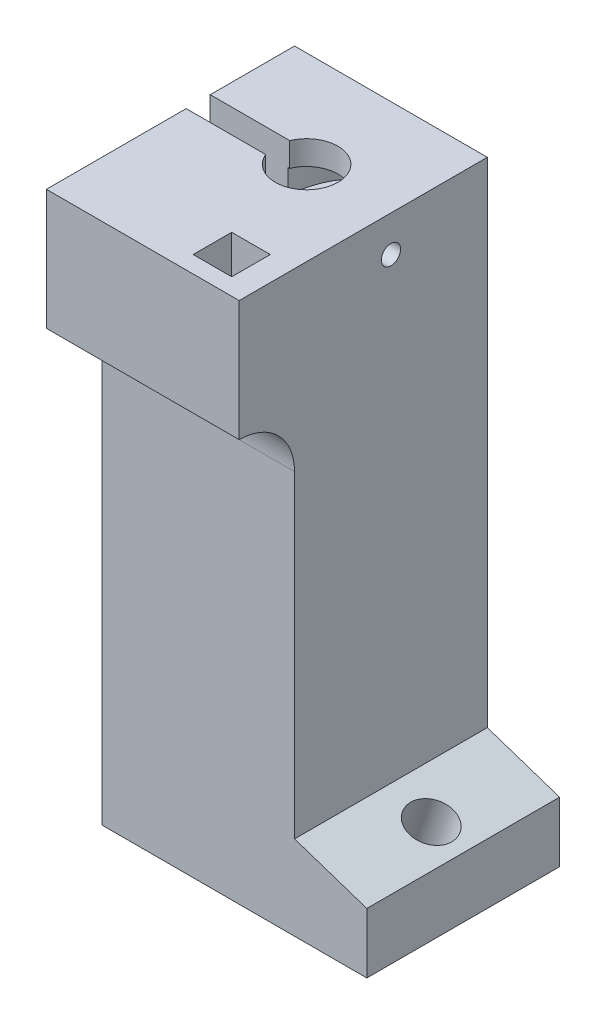
SolidWorks part; units mm, degrees
ref_plane "Front Plane" through (0, 0, 0) normal (0, 0, 1) x (1, 0, 0)
ref_plane "Top Plane" through (0, 0, 0) normal (0, 1, 0) x (1, 0, 0)
ref_plane "Right Plane" through (0, 0, 0) normal (1, 0, 0) x (0, 0, -1)
sketch "VerticalAxis" plane through (0, 0, 0) normal (0, 0, 1) x (1, 0, 0)
  line L0 (0, 0) -> (0, 42.951) construction
sketch "MainRotationalDesign" plane through (13.9419, 0, 0) normal (0, 0, -1) x (0, -1, 0)
  line L2 (5, 13.9419) -> (26.7642, 13.9419) construction
  line L3 (0, 13.9419) -> (-19.7322, 13.9419)
  line L4 (-7.75, 13.9419) -> (-7.75, 7.1919)
  point P0 (0, 13.9419)
  point P4 (0, 0)
  point P5 (0, 0)
  point P10 (0, 0)
  point P11 (0, 0)
  point P14 (5.666, 13.9419)
  dimension "D4" = 7.75
  dimension "D3" = 6.75
ref_plane "SingleChannelBasePlane" through (0, 7.75, 0) normal (0, 1, 0) x (0.9967, 0, 0.0811)
sketch "ShuttleOutline" plane through (-33.8949, 7.75, -2.7565) normal (0, 1, 0) x (0.9967, 0, 0.0811)
  line L0 (33.946, 0.7475) -> (38.9052, 1.4518) construction
  line L3 (39.0755, -0.6413) -> (34.0676, -0.7475) construction
  line L4 (36.4256, 1.0997) -> (36.9215, 1.1701)
  line L7 (36.9215, 1.1701) -> (36.9515, 0.8013)
  line L8 (36.4256, 1.0997) -> (33.9338, 0.897)
  line L9 (36.4256, 1.0997) -> (36.5715, -0.6944) construction
  line L10 (36.5715, -0.6944) -> (34.0797, -0.897)
  line L11 (33.9338, 0.897) -> (34.0797, -0.897) construction
  line L12 (36.9191, 1.2) -> (37.4175, 1.2405) construction
  line L13 (36.9191, 1.2) -> (36.9515, 0.8013) construction
  line L14 (36.9515, 0.8013) -> (37.4499, 0.8419)
  line L15 (37.4175, 1.2405) -> (37.4499, 0.8419)
  line L16 (37.5407, -0.2745) -> (37.0423, -0.315)
  line L17 (37.5407, -0.2745) -> (37.5731, -0.6731)
  line L18 (37.5731, -0.6731) -> (37.0747, -0.7137) construction
  line L19 (37.0423, -0.315) -> (37.0747, -0.7137) construction
  line L21 (36.5715, -0.6944) -> (37.0723, -0.6838)
  line L22 (37.0723, -0.6838) -> (37.0423, -0.315)
  line L23 (37.4175, 1.2405) -> (38.9052, 1.4518)
  line L24 (39.0755, -0.6413) -> (37.5731, -0.6731)
  line L25 (37.3414, 0.2712) -> (32.4051, -0.1303) construction
  line L26 (38.9052, 1.4518) -> (39.0755, -0.6413) construction
  line L27 (33.946, 0.7475) -> (34.0676, -0.7475) construction
  line L31 (34.0068, 0) -> (40.7346, 0.5471) construction
  circle A2 centre (38.9903, 0.4053) radius 0.6 construction
  circle A3 centre (38.9903, 0.4053) radius 0.4 construction
  circle A4 centre (34.0068, 0) radius 0.35 construction
  circle A5 centre (38.9903, 0.4053) radius 1.05 construction
  circle A6 centre (34.0068, 0) radius 0.75 construction
  arc A7 (33.9338, 0.897) -> (34.0797, -0.897) centre (34.0068, 0) ccw
  arc A8 (38.9052, 1.4518) -> (39.0755, -0.6413) centre (38.9903, 0.4053) cw
  point P4 (37.0723, -0.6838)
  point P15 (34.0068, 0)
  point P16 (36.9215, 1.1701)
  dimension "D2" = 1.2
  dimension "D3" = 0.8
  dimension "D4" = 0.7
  dimension "D1" = 1.5
  dimension "D5" = 2.1
  dimension "D6" = 5
  dimension "D10" = 1.8
  dimension "D9" = 2.5
  dimension "D11" = 2.5
  dimension "D12" = 0.5
  dimension "D14" = 1.5
  dimension "D7" = 0.4
sketch "ShuttleChannelOutline" plane through (33.8949, 7.75, 2.7565) normal (0, -1, 0) x (-0.9967, 0, -0.0811)
  line L0 (29.1854, 2.3987) -> (28.8611, -1.5881) construction
  line L1 (27.1169, -1.4463) -> (31.1037, -1.7705)
  line L2 (27.1169, -1.4463) -> (27.4411, 2.5405)
  line L3 (27.4411, 2.5405) -> (31.428, 2.2163)
  line L4 (31.1037, -1.7705) -> (31.428, 2.2163)
  line L5 (34.0068, 0) -> (27.279, 0.5471) construction
  line L6 (29.1084, 1.4518) -> (28.9381, -0.6413) construction
  line L8 (-199311.2371, 16211.4774) -> (199377.5178, -16211.3364) construction
  point P13 (27.279, 0.5471)
  point P16 (31.2658, 0.2229)
  dimension "D2" = 4
  dimension "D1" = 4
extrude "ShuttleChannelBody-Extrude" add sketch "ShuttleChannelOutline" against normal blind 10
sketch "Sketch23" plane through (0, 17.75, 0) normal (0, 1, 0) x (0.9959, 0, -0.09)
  line L0 (6.5427, -2.5991) -> (6.9025, 1.3847)
  line L1 (6.9025, 1.3847) -> (2.9188, 1.7445)
  line L2 (2.9188, 1.7445) -> (2.5589, -2.2393)
  line L3 (2.5589, -2.2393) -> (6.5427, -2.5991)
  line L4 (2.5589, -2.2393) -> (2.9188, 1.7445) construction
  circle A0 centre (4.9797, -0.4498) radius 0.425
  point P6 (0, 0)
  dimension "D1" = 0.85
extrude "ShuttleChannelCap-Extrude1" add sketch "Sketch23" along normal blind 1
sketch "Sketch22" plane through (0, 18.75, 0) normal (0, 1, 0) x (0.9909, 0, -0.1349)
  line L0 (6.4185, -2.8923) -> (2.4551, -2.3527)
  line L1 (2.4551, -2.3527) -> (2.9947, 1.6107)
  line L2 (2.9947, 1.6107) -> (6.9581, 1.0711)
  line L3 (6.9581, 1.0711) -> (6.4185, -2.8923)
  line L4 (5.0959, 0.3659) -> (4.8127, -1.7149) construction
  line L5 (0, 0) -> (6.6883, -0.9106) construction
  circle A0 centre (4.9543, -0.6745) radius 0.65 construction
  ellipse E0 centre (4.9543, -0.6745) end of major axis (5.1297, 0.6136) minor radius 0.65
  dimension "D1" = 1.3
  dimension "D2" = 2.6
extrude "ShuttleChannelCap-Extrude2" add sketch "Sketch22" along normal blind 0.5
sketch "Sketch24" plane through (0, 19.25, 0) normal (0, 1, 0) x (0.9909, 0, -0.1349)
  line L0 (6.4185, -2.8923) -> (6.9581, 1.0711)
  line L1 (6.9581, 1.0711) -> (2.9947, 1.6107)
  line L2 (2.9947, 1.6107) -> (2.4551, -2.3527)
  line L3 (2.4551, -2.3527) -> (6.4185, -2.8923)
  circle A0 centre (4.9543, -0.6745) radius 0.65
  circle A1 centre (4.9543, -0.6745) radius 0.65 construction
extrude "ShuttleChannelCap-Extrude3" add sketch "Sketch24" along normal blind 0.5
sketch "Sketch25" plane through (0, 19.75, 0) normal (0, 1, 0) x (0.9909, 0, -0.1349)
  line L2 (2.9947, 1.6107) -> (2.4551, -2.3527) construction
  line L4 (2.7586, -0.1233) -> (4.3935, -0.3458)
  line L5 (4.3935, -0.3458) -> (4.3261, -0.8413)
  line L6 (4.3261, -0.8413) -> (2.6911, -0.6187)
  line L7 (2.6911, -0.6187) -> (2.7586, -0.1233)
  circle A0 centre (4.9543, -0.6745) radius 0.65 construction
  point P2 (2.7249, -0.371)
  dimension "D1" = 0.5
extrude "ShuttleChannelCap-InjectionChannel" cut sketch "Sketch25" against normal up to surface (1 mm away) up to face at (4.575, 18.75, 0)
sketch "Sketch26" plane through (6.75, 0, 0) normal (-1, 0, 0) x (0, -0.8752, -0.4838)
  line L0 (-6.7828, -3.7491) -> (-16.6288, -9.1914) construction
  line L1 (-7.7503, -1.9987) -> (-5.8153, -5.4995) construction
  line L3 (-18.2528, -7.8038) -> (-16.3177, -11.3046) construction
  circle A0 centre (-16.6288, -9.1914) radius 0.2
  dimension "D1" = 0.4
  dimension "D2" = 0.75
extrude "ShuttleChannelCap-InjectionHole" cut sketch "Sketch26" along normal through all
fillet "ShuttleChannelCap-InjectionHole-Fillet" radius 0.25 1 edges at (5.6427, 18.9547, 0.1948)
extrude "Channel-Cut-Extrude12" cut sketch "ShuttleOutline" along normal blind 10 and the other way blind 5
fillet "Fillet1" radius 0.125 4 edges at (3, 12.75, 0.56) (3.5, 12.75, 0.56) (3.5, 12.75, -0.56) (3, 12.75, -0.56)
sketch "Sketch27" plane through (0, 0, 2) normal (0, 0, 1) x (1, 0, 0)
  line L0 (6.75, 7.75) -> (8.25, 7.75)
  line L1 (8.25, 7.75) -> (8.25, 9)
  line L2 (8.25, 9) -> (6.75, 9.5)
  line L3 (6.75, 19.75) -> (6.75, 7.75) construction
  line L4 (6.75, 9.5) -> (6.75, 7.75)
  dimension "D1" = 1.5
  dimension "D2" = 1.25
  dimension "D3" = 1.75
extrude "Boss-Extrude1" add sketch "Sketch27" against normal up to surface (4 mm away) up to face at (4.75, 13.75, -2)
sketch "Sketch28" plane through (3.525, 10.575, 0) normal (0.3162, 0.9487, 0) x (0.9487, -0.3162, 0)
  line L0 (4.9806, 0) -> (4.2806, 0) construction
  line L1 (4.9806, 2) -> (4.9806, -2) construction
  circle A0 centre (4.2806, 0) radius 0.45
  dimension "D1" = 0.9
  dimension "D2" = 0.7
extrude "Cut-Extrude1" cut sketch "Sketch28" against normal through all contours A0
sketch "Sketch29" plane through (0, 0, 2) normal (0, 0, 1) x (1, 0, 0)
  line L0 (2.75, 19.75) -> (2.75, 7.75) construction
  line L1 (6.75, 19.75) -> (2.75, 19.75)
  line L2 (6.75, 19.75) -> (6.75, 17.25)
  line L3 (6.75, 17.25) -> (2.75, 17.25)
  line L4 (2.75, 19.75) -> (2.75, 17.25)
  dimension "D1" = 2.5
extrude "Boss-Extrude2" add sketch "Sketch29" along normal blind 1.15
fillet "Fillet2" radius 1.15 1 edges at (4.75, 17.25, 2)
sketch "Sketch30" plane through (0, 19.75, 0) normal (0, 1, 0) x (1, 0, 0)
  line L0 (6.75, -2) -> (2.75, -2) construction
  line L1 (6.2452, -2.8) -> (5.4452, -2.8)
  line L2 (6.2452, -2.8) -> (6.2452, -2)
  line L3 (6.2452, -2) -> (5.4452, -2)
  line L4 (5.4452, -2.8) -> (5.4452, -2)
  dimension "D1" = 0.8
extrude "Cut-Extrude2" cut sketch "Sketch30" against normal blind 2
equation "\"DriveAngle\"= 37.5"
equation "\"WidthExtensionHalfOffset\"= 2.2mm"
equation "\"RotationMarginAngle\"= 17.5deg"
equation "\"Rotation\"= 180 - 2 * \"RotationMarginAngle\""
equation "\"DriveVerticalOffset\"= 5"
equation "\"ShuttleChannelBackWall\"= 1.75"
equation "\"ShuttleHoleSeparation\"=5"
equation "\"D6@ShuttleOutline\"=\"ShuttleHoleSeparation\""
equation "\"ElectrodePathToWall\"= \"ShuttleHoleSeparation\" + \"ShuttleChannelBackWall\""
equation "\"D3@MainRotationalDesign\"=\"ElectrodePathToWall\""
equation "\"ScrewHeadDiameter\"=1.3"
equation "\"D1@Sketch22\"=\"ScrewHeadDiameter\""
equation "\"D2@Sketch22\"=2*\"ScrewHeadDiameter\""
equation "\"ScrewFreeDiameter\"=0.85"
equation "\"D1@Sketch23\"=\"ScrewFreeDiameter\""
equation "\"ChannelWidth\"= 4"
equation "\"D2@ShuttleChannelOutline\"=\"ChannelWidth\""
equation "\"ChannelDepth\"=4"
equation "\"D1@ShuttleChannelOutline\"=\"ChannelDepth\""
equation "\"FullConnectedHeight\"=6"
equation "\"ActualOffset\"=7.75"
equation "\"D4@MainRotationalDesign\"=\"ActualOffset\""
equation "\"LooseTapDrill0_80\"=1.52"
equation "\"EIB_Mount_Screw_Head\"=2.54"
equation "\"TapDrill0_80\"=1.19"
equation "\"StimElectrodeBendAngle\"=24"
equation "\"ChannelTravel\"= 10"
equation "\"D1@ShuttleChannelBody-Extrude\"=\"ChannelTravel\""
equation "\"StimChannelTravel\"= 15"
equation "\"D1\"= \"StimChannelTravel\""
equation "\"D1@Channel-Cut-Extrude12\" = \"ChannelTravel\""
